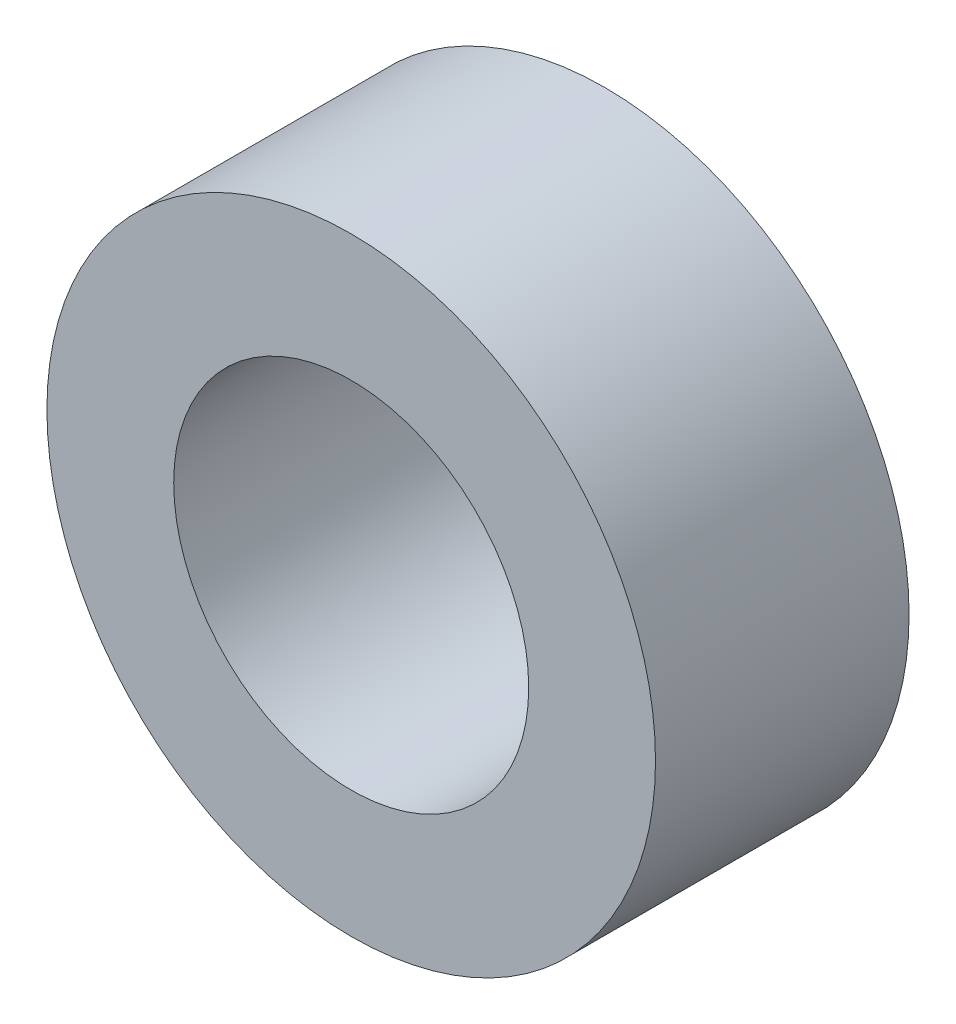
SolidWorks part; units mm, degrees
ref_plane "Front Plane" through (0, 0, 0) normal (0, 0, 1) x (1, 0, 0)
ref_plane "Top Plane" through (0, 0, 0) normal (0, 1, 0) x (1, 0, 0)
ref_plane "Right Plane" through (0, 0, 0) normal (1, 0, 0) x (0, 0, -1)
ref_plane "Plane1" through (0, 0, 5) normal (0, 0, 1) x (1, 0, 0)
sketch "Sketch1" plane through (0, 0, 5) normal (0, 0, 1) x (1, 0, 0)
  circle A0 centre (0, 0) radius 6
  circle A1 centre (0, 0) radius 3.5
extrude "Boss-Extrude1" add sketch "Sketch1" against normal blind 5
ref_axis "Axis1" through (0, 0, -3.1895) along (0, 0, 1)
